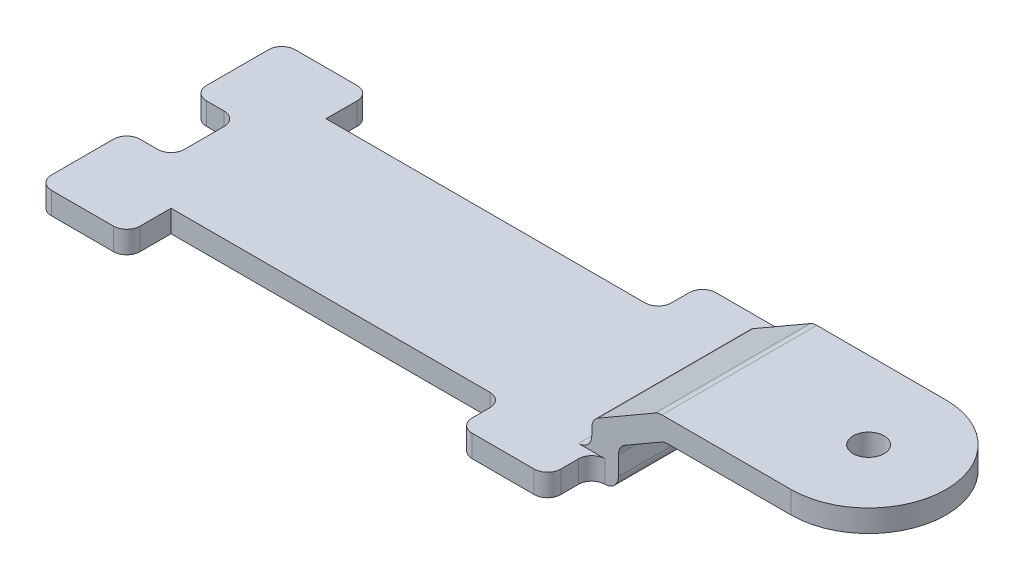
SolidWorks part; units mm, degrees
material "PEI"
ref_plane "Front Plane" through (0, 0, 0) normal (0, 0, 1) x (1, 0, 0)
ref_plane "Top Plane" through (0, 0, 0) normal (0, 1, 0) x (1, 0, 0)
ref_plane "Right Plane" through (0, 0, 0) normal (1, 0, 0) x (0, 0, -1)
sketch "Sketch1" plane through (0, 0, 0) normal (0, 0, 1) x (1, 0, 0)
  line L0 (-121, 0) -> (-121, 5)
  line L1 (-121, 5) -> (-6, 5)
  line L2 (-6, 5) -> (-6, 11.3397)
  line L3 (-6, 11.3397) -> (9, 20)
  line L4 (9, 20) -> (59, 20)
  line L5 (59, 20) -> (59, 15)
  line L6 (59, 15) -> (10.3397, 15)
  line L7 (10.3397, 15) -> (0, 9.0303)
  line L8 (0, 9.0303) -> (0, 0)
  line L9 (0, 0) -> (-121, 0)
  dimension "D1" = 5
  dimension "D2" = 6
  dimension "D3" = 5
  dimension "D4" = 5
  dimension "D5" = 115
  dimension "D6" = 50
  dimension "D7" = 15
  dimension "D8" = 180
  dimension "D9" = 30
extrude "Boss-Extrude1" add sketch "Sketch1" along normal mid plane 55
sketch "Sketch3" plane through (0, 20, 0) normal (0, 1, 0) x (1, 0, 0)
  line L1 (-121, 27.5) -> (-121, -27.5) construction
  line L2 (-121, -27.5) -> (-6, -27.5) construction
  line L3 (-6, -27.5) -> (-6, 27.5) construction
  line L4 (9, 27.5) -> (-6, 27.5) construction
  line L5 (-6, 27.5) -> (-6, -27.5) construction
  line L6 (-6, -27.5) -> (9, -27.5) construction
  line L7 (59, 27.5) -> (9, 27.5) construction
  line L8 (9, -27.5) -> (59, -27.5) construction
  line L9 (59, -27.5) -> (59, 27.5) construction
  line L11 (-121, 27.5) -> (-121, -27.5)
  line L12 (-121, -27.5) -> (-6, -27.5)
  line L13 (-6, -27.5) -> (-6, 27.5)
  line L14 (9, 27.5) -> (-6, 27.5)
  line L15 (-6, 27.5) -> (-6, -27.5)
  line L16 (-6, -27.5) -> (9, -27.5)
  line L17 (59, 27.5) -> (9, 27.5)
  line L18 (9, -27.5) -> (59, -27.5)
  line L19 (59, -27.5) -> (59, 27.5)
  line L20 (-121, 0) -> (39, 0)
  line L21 (39, 17.5) -> (-6, 17.5)
  line L22 (39, -17.5) -> (-6, -17.5)
  line L23 (-101, 17.5) -> (-26, 17.5)
  line L24 (-121, 27.5) -> (-101, 27.5)
  line L25 (-121, 27.5) -> (-121, 7.5)
  line L26 (-121, 7.5) -> (-101, 7.5)
  line L27 (-101, 27.5) -> (-101, 7.5)
  line L28 (-121, -27.5) -> (-101, -27.5)
  line L29 (-121, -27.5) -> (-121, -7.5)
  line L30 (-121, -7.5) -> (-101, -7.5)
  line L31 (-101, -27.5) -> (-101, -7.5)
  line L33 (-6, 27.5) -> (-6, 17.5)
  line L36 (-6, -27.5) -> (-26, -27.5)
  line L37 (-6, -27.5) -> (-6, -7.5)
  line L38 (-6, -7.5) -> (-26, -7.5)
  line L39 (-26, -27.5) -> (-26, -7.5)
  line L40 (-6, 27.5) -> (-26, 27.5)
  line L41 (-6, 27.5) -> (-6, 7.5)
  line L42 (-6, 7.5) -> (-26, 7.5)
  line L43 (-26, 27.5) -> (-26, 7.5)
  line L44 (-111, 7.5) -> (-111, -7.5)
  line L45 (-101, 27.5) -> (-6, 27.5)
  line L46 (-26, -17.5) -> (-101, -17.5)
  line L47 (-16, -7.5) -> (-16, 7.5)
  circle A0 centre (39, 0) radius 12.5
  circle A1 centre (39, 0) radius 17.5
  circle A2 centre (39, 0) radius 3.5
  line M15 (59, 27.5) -> (9, 27.5)
  line M16 (9, 27.5) -> (9, -27.5)
  line M17 (9, -27.5) -> (59, -27.5)
  line M18 (59, -27.5) -> (59, 27.5)
  dimension "D2" = 25
  dimension "D12" = 7
  dimension "D1" = 160
  dimension "D4" = 20
  dimension "D5" = 20
  dimension "D6" = 20
  dimension "D7" = 20
  dimension "D8" = 20
  dimension "D9" = 20
  dimension "D10" = 20
  dimension "D11" = 20
  dimension "D3" = 5
extrude "Cut-Extrude2" cut sketch "Sketch3" against normal blind 55 contours A2 | A1 L22 L21 M16 M17 M18 M15 | L21 L14 L13 M16 | L22 L13 L16 M16 | L39 L46 L31 L12 | L45 L27 L23 L43 | L44 L26 L11 L20 | L44 L20 L11 L30 region at (-116, 20, -3.75) region at (-63.5, 20, -22.5) region at (-116, 20, 3.75) region at (1.5, 20, -22.5) region at (34, 20, -26.7567) region at (-63.5, 20, 22.5) region at (39, 20, -3.401) region at (1.5, 20, 22.5)
fillet "Fillet6" radius 3 14 edges at (-6, 2.5, 27.5) (-26, 2.5, 27.5) (-26, 2.5, 17.5) (-6, 2.5, -27.5) (-26, 2.5, -27.5) (-26, 2.5, -17.5) (-121, 2.5, -7.5) (-111, 2.5, -7.5) (-111, 2.5, 7.5) (-121, 2.5, 7.5) (-121, 2.5, 27.5) (-101, 2.5, 27.5) (-101, 2.5, -27.5) (-121, 2.5, -27.5)
fillet "Fillet7" radius 3 7 edges at (10.3397, 15, 0) (9, 20, 0) (-6, 11.3397, 0) (0, 9.0303, 0) (0, 0, 0) (-6, 2.5, -17.5) (-6, 2.5, 17.5)
fillet "Fillet8" radius 3 1 edges at (-6, 5, 0)
